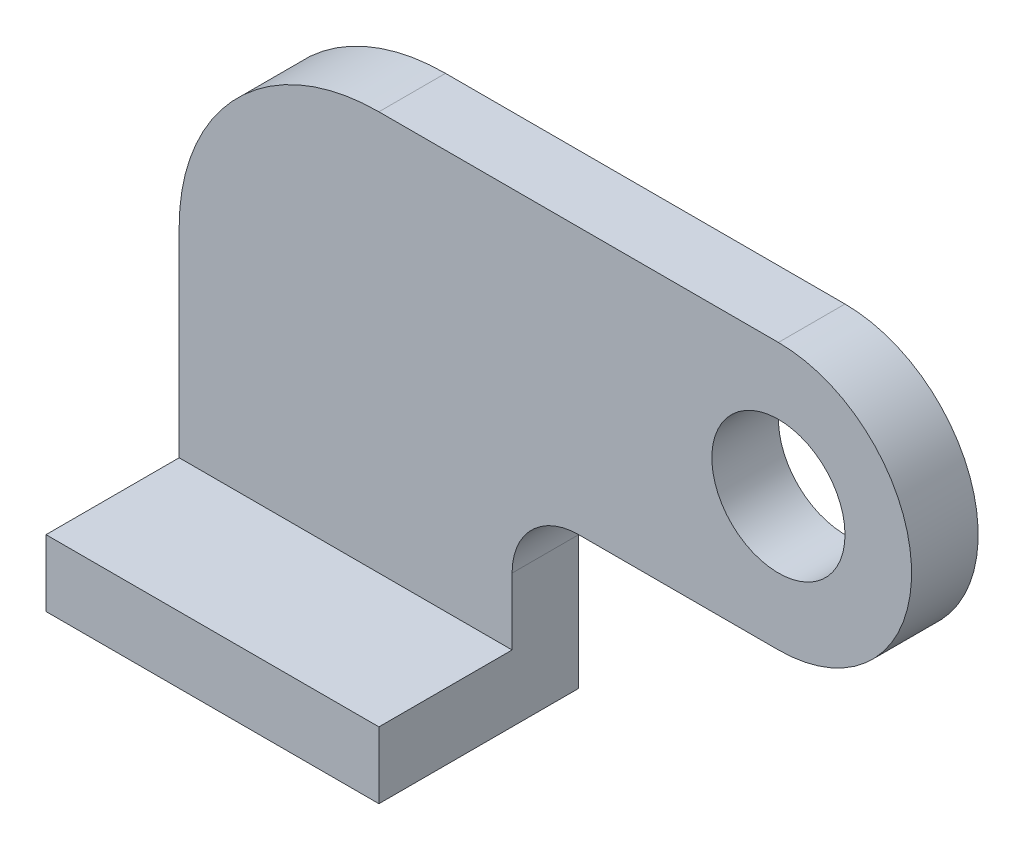
SolidWorks part; units mm, degrees
material "Plain Carbon Steel"
ref_plane "Front Plane" through (0, 0, 0) normal (0, 0, 1) x (1, 0, 0)
ref_plane "Top Plane" through (0, 0, 0) normal (0, 1, 0) x (1, 0, 0)
ref_plane "Right Plane" through (0, 0, 0) normal (1, 0, 0) x (0, 0, -1)
sketch "Sketch1" plane through (0, 0, 0) normal (0, 0, 1) x (1, 0, 0)
  line L0 (0, 12.7) -> (0, 50.8)
  line L1 (0, 0) -> (63.5, 0)
  line L2 (0, 0) -> (0, 12.7)
  line L3 (0, 12.7) -> (63.5, 12.7)
  line L4 (63.5, 0) -> (63.5, 12.7)
  line L5 (38.1, 88.9) -> (114.3, 88.9)
  line L6 (63.5, 12.7) -> (63.5, 25.4)
  line L7 (76.2, 38.1) -> (114.3, 38.1)
  line L8 (114.3, 38.1) -> (114.3, 88.9)
  circle A0 centre (114.3, 63.5) radius 25.4
  circle A1 centre (114.3, 63.5) radius 12.7
  arc A2 (63.5, 25.4) -> (76.2, 38.1) centre (76.2, 25.4) cw
  arc A3 (0, 50.8) -> (38.1, 88.9) centre (38.1, 50.8) cw
  point P13 (63.5, 38.1)
  dimension "D6" = 25.4
  dimension "D7" = 12.7
  dimension "D8" = 38.1
  dimension "D1" = 63.5
  dimension "D2" = 50.8
  dimension "D3" = 12.7
  dimension "D4" = 88.9
  dimension "D5" = 50.8
extrude "Boss-Extrude1" add sketch "Sketch1" along normal blind 38.1 contours L1 L4 L3 L2 region at (31.75, 6.35, 0)
extrude "Boss-Extrude2" add sketch "Sketch1<4>" along normal blind 12.7 contours A3 L0 L3 L6 A2 L7 A0 L5 | A1 L8 A0 | A1 L8 A0 region at (45.3227, 52.4558, 0) region at (131.8589, 81.0589, 0) region at (113.732, 82.55, 0)
sketch "Sketch1<4>" plane through (0, 0, 0) normal (0, 0, 1) x (1, 0, 0) same geometry as "Sketch1"
